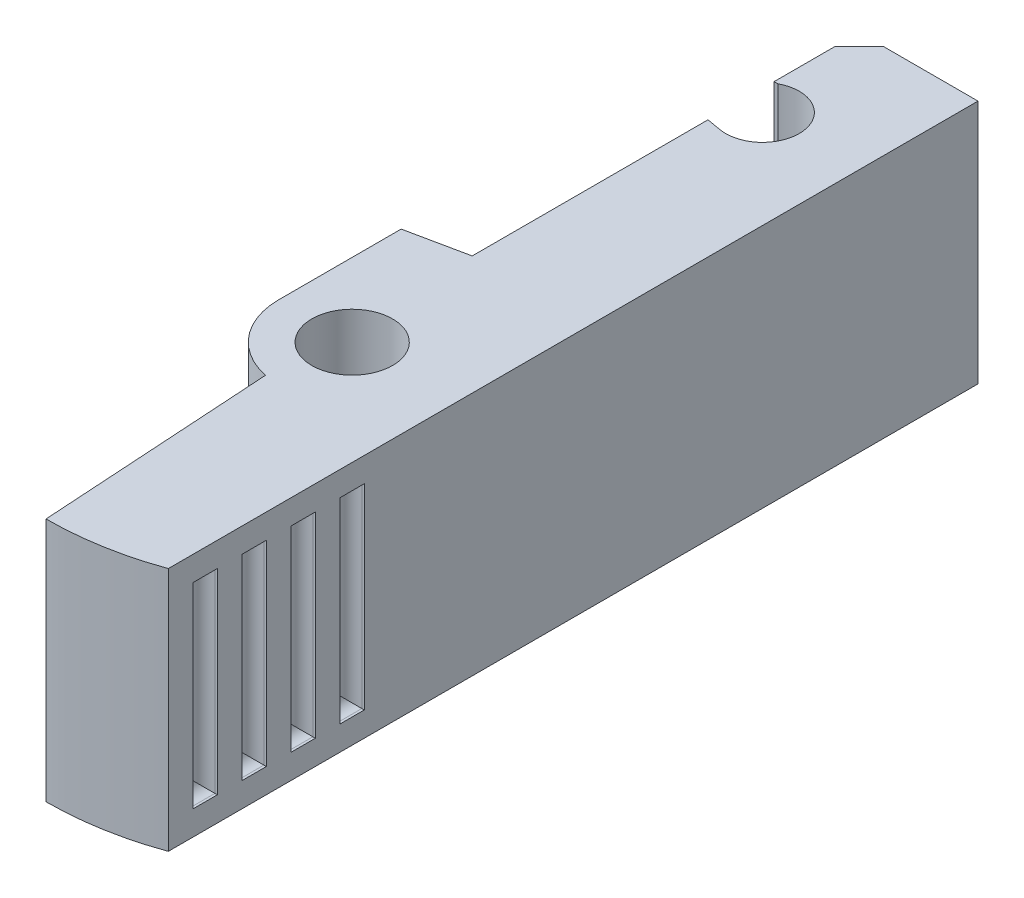
SolidWorks part; units mm, degrees
ref_plane "Front Plane" through (0, 0, 0) normal (0, 0, 1) x (1, 0, 0)
ref_plane "Top Plane" through (0, 0, 0) normal (0, 1, 0) x (1, 0, 0)
ref_plane "Right Plane" through (0, 0, 0) normal (1, 0, 0) x (0, 0, -1)
sketch "Sketch1" plane through (0, 0, 0) normal (0, 1, 0) x (1, 0, 0)
  line L0 (0, -18.6887) -> (0, 17.743) construction
  line L1 (-8.8335, 16.5) -> (8.9277, 16.5) construction
  line L2 (-9.6992, 0) -> (9.6992, 0) construction
  line L3 (-9.7784, -12.5) -> (9.7784, -12.5) construction
  line L4 (4.25, 21.3) -> (4.25, -17.7645) construction
  line L7 (4.25, 21.3) -> (4.25, -11.7553)
  line L9 (0, -12.5) -> (-0.6, -2.9394)
  line L10 (-3, 18.2158) -> (-3, -18.2158) construction
  line L11 (-0.6, 20.3) -> (-0.6, -18.2158) construction
  line L12 (-0.6, 15.1268) -> (-0.6, 5.5)
  line L13 (-0.6, 5.5) -> (-3, 5)
  line L14 (-3, 5) -> (-3, 0)
  line L15 (-0.6, 17.8266) -> (-0.6, 20.3)
  line L16 (-0.6, 20.3) -> (0.4, 21.3)
  line L17 (0.4, 21.3) -> (4.25, 21.3)
  line L19 (0.25, 21.3) -> (0.25, 13.2183) construction
  line L20 (-0.6, 15.1268) -> (0, 15.021)
  line L21 (-0.6, 17.8266) -> (-0.45, 17.8266)
  circle A0 centre (0, 0) radius 1.65
  arc A2 (-0.6, -2.9394) -> (-3, 0) centre (0, 0) cw
  arc A3 (0, -12.5) -> (4.25, -11.7553) centre (0, 0) ccw
  arc A5 (0, 15.021) -> (-0.45, 17.8266) centre (0.25, 16.5) ccw
  point P10 (0, -12.5)
  dimension "D3" = 3.3
  dimension "D5" = 5
  dimension "D8" = 80
  dimension "D15" = 1.5
  dimension "D1" = 16.5
  dimension "D2" = 12.5
  dimension "D4" = 4.25
  dimension "D6" = 3
  dimension "D7" = 0.6
  dimension "D9" = 135
  dimension "D10" = 11
  dimension "D11" = 0.25
  dimension "D12" = 4.8
  dimension "D13" = 135
  dimension "D14" = 0.4
  dimension "D16" = 0.15
  dimension "D17" = 9.6268
  dimension "D18" = 2.4734
extrude "Boss-Extrude1" add sketch "Sketch1" along normal blind 10
sketch "Sketch2" plane through (4.25, 0, 0) normal (1, 0, 0) x (0, 0, -1)
  line L0 (-16.2424, 5) -> (17.4778, 5) construction
  line L1 (20.3, 0) -> (-18.2158, 0) construction
  line L2 (0, 0) -> (0, 10) construction
  line L3 (-11.7553, 10) -> (21.3, 10) construction
  line L4 (-7, 10) -> (-7, 0) construction
  line L5 (21.3, 0) -> (-11.7553, 0) construction
  circle A0 centre (-7, 5) radius 2.5
  dimension "D3" = 5
  dimension "D1" = 5
  dimension "D2" = 7
extrude "Cut-Extrude1" cut sketch "Sketch2" against normal blind 10 from offset 2 offset against normal yes
sketch "Sketch3" plane through (4.25, 0, 0) normal (1, 0, 0) x (0, 0, -1)
  line L0 (-11.7553, 10) -> (-11.7553, 0) construction
  line L1 (-10.7553, 9) -> (-9.7553, 9)
  line L2 (-10.7553, 9) -> (-10.7553, 1)
  line L3 (-10.7553, 1) -> (-9.7553, 1)
  line L4 (-9.7553, 9) -> (-9.7553, 1)
  line L5 (-8.7553, 9) -> (-7.7553, 9)
  line L6 (-8.7553, 9) -> (-8.7553, 1)
  line L7 (-8.7553, 1) -> (-7.7553, 1)
  line L8 (-7.7553, 9) -> (-7.7553, 1)
  line L9 (-6.7553, 9) -> (-5.7553, 9)
  line L10 (-6.7553, 9) -> (-6.7553, 1)
  line L11 (-6.7553, 1) -> (-5.7553, 1)
  line L12 (-5.7553, 9) -> (-5.7553, 1)
  line L13 (-11.7553, 10) -> (21.3, 10) construction
  line L14 (18.2158, 0) -> (-18.2158, 0) construction
  line L16 (-4.7553, 9) -> (-3.7553, 9)
  line L17 (-4.7553, 9) -> (-4.7553, 1)
  line L18 (-4.7553, 1) -> (-3.7553, 1)
  line L19 (-3.7553, 9) -> (-3.7553, 1)
  point P14 (-10.2553, 9)
  dimension "D1" = 1
  dimension "D2" = 1
  dimension "D3" = 1
  dimension "D4" = 1
  dimension "D5" = 1
  dimension "D6" = 1
  dimension "D7" = 1
  dimension "D8" = 1
  dimension "D9" = 1
  dimension "D10" = 1
  dimension "D11" = 1
  dimension "D12" = 1
  dimension "D13" = 1
  dimension "D14" = 1
  dimension "D15" = 1
  dimension "D16" = 1
extrude "Cut-Extrude2" cut sketch "Sketch3" against normal blind 0.6
fillet "Fillet1" radius 0.5 16 edges at (3.65, 9, 4.2553) (3.65, 5, 3.7553) (3.65, 1, 4.2553) (3.65, 5, 4.7553) (3.65, 9, 6.2553) (3.65, 5, 5.7553) (3.65, 1, 6.2553) (3.65, 5, 6.7553) (3.65, 9, 8.2553) (3.65, 5, 7.7553) (3.65, 1, 8.2553) (3.65, 5, 8.7553) (3.65, 9, 10.2553) (3.65, 5, 9.7553) (3.65, 1, 10.2553) (3.65, 5, 10.7553)
